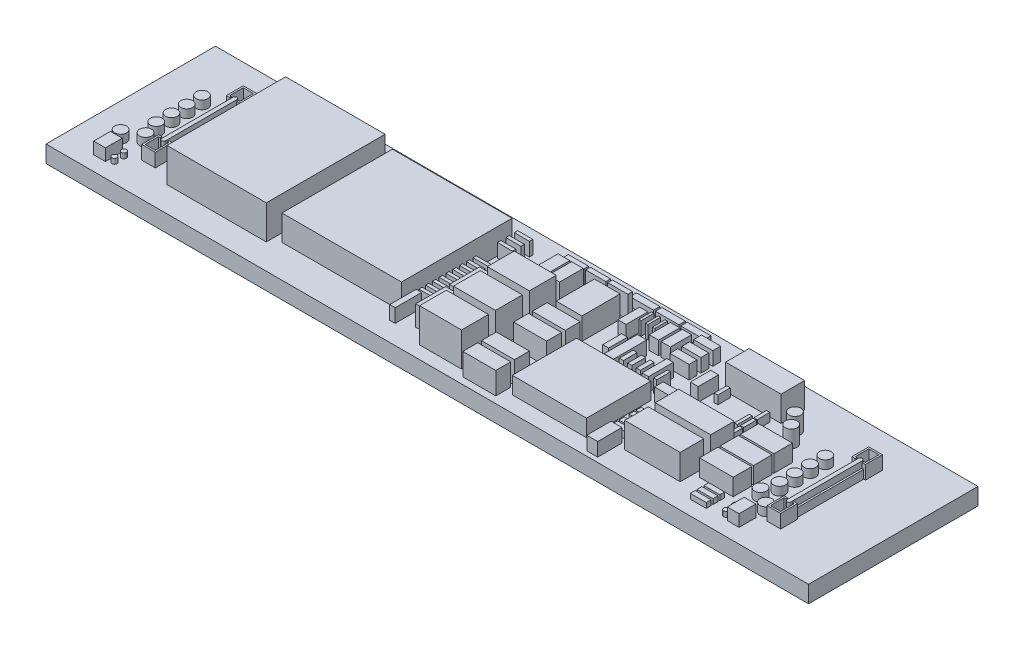
SolidWorks part; units mm, degrees
material "A-Glass Fiber"
ref_plane "Front Plane" through (0, 0, 0) normal (0, 0, 1) x (1, 0, 0)
ref_plane "Top Plane" through (0, 0, 0) normal (0, 1, 0) x (1, 0, 0)
ref_plane "Right Plane" through (0, 0, 0) normal (1, 0, 0) x (0, 0, -1)
sketch "Sketch1" plane through (0, 0, 0) normal (0, 1, 0) x (1, 0, 0)
  line L1 (22.5, 5) -> (-22.5, 5)
  line L2 (22.5, 5) -> (22.5, -5)
  line L3 (22.5, -5) -> (-22.5, -5)
  line L4 (-22.5, 5) -> (-22.5, -5)
  line L5 (22.5, 5) -> (-22.5, -5) construction
  line L6 (22.5, -5) -> (-22.5, 5) construction
  point P0 (0, 0)
  dimension "D1" = 10
  dimension "D2" = 45
extrude "Boss-Extrude1" add sketch "Sketch1" along normal blind 1
sketch "Sketch7" plane through (0, 1, 0) normal (0, 1, 0) x (1, 0, 0)
  line L0 (18.0549, 3) -> (18.8549, 3)
  line L1 (18.8549, 3) -> (18.8549, 2)
  line L2 (18.0549, 3) -> (18.0549, 2)
  line L3 (18.0549, 2) -> (18.2549, 2)
  line L5 (18.8549, 2) -> (18.6549, 2)
  line L6 (18.6549, 2) -> (18.6549, 0)
  line L7 (18.3549, 2.1) -> (18.3549, 0)
  line L8 (22.5, 5) -> (-22.5, 5) construction
  line L9 (22.5, 0) -> (-21.2933, 0) construction
  line L10 (22.5, -5) -> (22.5, 5) construction
  line L11 (18.1549, 2.1) -> (18.2549, 2.1)
  line L12 (18.1549, 2.9) -> (18.1549, 2.1)
  line L13 (18.1549, 2.9) -> (18.7549, 2.9)
  line L14 (18.7549, 2.9) -> (18.7549, 2.1)
  line L15 (18.7549, 2.1) -> (18.6549, 2.1)
  line L16 (18.5549, 2.1) -> (18.5549, 0)
  line L17 (18.2549, 2) -> (18.2549, 2.1)
  line L18 (18.6549, 2) -> (18.6549, 2.1)
  line L19 (18.1549, 2.1) -> (18.3549, 2.1) construction
  line L20 (18.7549, 2.1) -> (18.5549, 2.1) construction
  line L21 (18.2549, 2) -> (18.2549, 0) construction
  dimension "D1" = 1
  dimension "D2" = 0.8
  dimension "D3" = 0.2
  dimension "D4" = 0.2
  dimension "D5" = 2
  dimension "D6" = 0.1
extrude "Boss-Extrude4" add sketch "Sketch7" along normal blind 0.8 contours L18 L5 L1 L0 L2 L3 L17 L11 L12 L13 L14 L15 region at (18.4549, 1, -2.9872)
sketch "Sketch8" plane through (0, 1, 0) normal (0, 1, 0) x (1, 0, 0)
  line L0 (18.1549, 2) -> (18.1549, -2)
  line L1 (18.0549, 2) -> (18.2549, 2) construction
  line L3 (18.2647, -2) -> (18.2647, 2)
  line L4 (18.0549, 2) -> (18.2549, 2) construction
  line L5 (18.2647, 2) -> (18.1549, 2)
  line L6 (18.1549, -2) -> (18.2647, -2)
  line L8 (18.645, 2) -> (18.7549, 2)
  line L9 (18.645, -2) -> (18.645, 2)
  line L10 (18.7549, 2) -> (18.7549, -2)
  line L11 (22.5, 0) -> (-0.6282, 0) construction
  line L12 (22.5, -5) -> (22.5, 5) construction
  line L13 (18.645, -2) -> (18.7549, -2)
  point P9 (18.7549, 0)
  point P11 (18.645, 0)
  point P15 (18.2647, 0)
  point P23 (18.1549, 0)
extrude "Boss-Extrude5" add sketch "Sketch8" along normal blind 0.5
mirror "Mirror1" about plane through (0, 0, 0) normal (0, 0, 1) of "Boss-Extrude4"
sketch "Sketch9" plane through (0, 1, 0) normal (0, 1, 0) x (1, 0, 0)
  line L0 (18.4549, 2.1) -> (18.4549, -2.1) construction
  line L2 (18.4549, 2.1) -> (18.4549, -2.1) construction
  line L3 (18.5737, 2.1) -> (18.5737, -2.1)
  line L4 (18.336, 2.1) -> (18.336, -2.1)
  arc A0 (18.5737, 2.1) -> (18.336, 2.1) centre (18.4549, 2.1) ccw
  arc A1 (18.336, -2.1) -> (18.5737, -2.1) centre (18.4549, -2.1) ccw
  point P2 (18.4549, 0)
extrude "Boss-Extrude6" add sketch "Sketch9" along normal blind 0.8
mirror "Mirror2" about plane through (0, 0, 0) normal (1, 0, 0) of "Boss-Extrude6", "Mirror1", "Boss-Extrude5", "Boss-Extrude4"
sketch "Sketch10" plane through (0, 1, 0) normal (0, 1, 0) x (1, 0, 0)
  line L0 (16.8488, -4.144) -> (17.5436, -4.144)
  line L1 (17.5436, -4.144) -> (17.5436, -3.1514)
  line L2 (17.5436, -3.1514) -> (16.8488, -3.1514)
  line L3 (16.8488, -3.1514) -> (16.8488, -4.144)
extrude "Boss-Extrude7" add sketch "Sketch10" along normal blind 0.7
sketch "Sketch11" plane through (0, 1, 0) normal (0, 1, 0) x (1, 0, 0)
  circle A0 centre (17.5436, -2.5555) radius 0.35
  circle A1 centre (16.5477, -3.908) radius 0.15
  circle A2 centre (16.5477, -3.3563) radius 0.15
  dimension "D1" = 0.7
  dimension "D2" = 0.3
  dimension "D3" = 0.3
extrude "Boss-Extrude8" add sketch "Sketch11" along normal blind 0.5 contours A0 region at (17.5436, 1, 2.5555)
extrude "Boss-Extrude9" add sketch "Sketch11<3>" along normal blind 0.3 contours A1 | A2 region at (16.5477, 1, 3.908) region at (16.5477, 1, 3.3563)
sketch "Sketch11<3>" plane through (0, 1, 0) normal (0, 1, 0) x (1, 0, 0) same geometry as "Sketch11"
sketch "Sketch12" plane through (0, 1, 0) normal (0, 1, 0) x (1, 0, 0)
  circle A0 centre (16.6479, -1.9784) radius 0.35
  circle A1 centre (16.8903, -1.103) radius 0.35
  circle A2 centre (16.8903, -0.203) radius 0.35
  circle A3 centre (16.8903, 0.697) radius 0.35
  circle A4 centre (16.8903, 1.597) radius 0.35
  dimension "D1" = 0.7
  dimension "D2" = 0.7
  dimension "D3" = 4
extrude "Boss-Extrude10" add sketch "Sketch12" along normal blind 0.5
sketch "Sketch13" plane through (0, 1, 0) normal (0, 1, 0) x (1, 0, 0)
  line L0 (16.8488, -4.144) -> (-26.6256, -4.144) construction
  line L1 (14.6652, -4.144) -> (15.6081, -4.144)
  line L2 (15.6081, -4.144) -> (15.6081, -3.8538)
  line L3 (15.6081, -3.8538) -> (14.6652, -3.8538)
  line L4 (14.6652, -3.8538) -> (14.6652, -4.144)
  line L5 (14.6652, -3.4538) -> (14.6652, -3.744)
  line L6 (14.6652, -3.744) -> (15.6081, -3.744)
  line L7 (15.6081, -3.744) -> (15.6081, -3.4538)
  line L8 (15.6081, -3.4538) -> (14.6652, -3.4538)
  line L9 (14.6652, -3.0538) -> (14.6652, -3.344)
  line L10 (14.6652, -3.344) -> (15.6081, -3.344)
  line L11 (15.6081, -3.344) -> (15.6081, -3.0538)
  line L12 (15.6081, -3.0538) -> (14.6652, -3.0538)
  dimension "D1" = 3
extrude "Boss-Extrude11" add sketch "Sketch13" along normal blind 0.3
sketch "Sketch14" plane through (0, 1, 0) normal (0, 1, 0) x (1, 0, 0)
  line L0 (13.8215, -0.4625) -> (15.8066, -1.5544) construction
  line L1 (13.8215, -1.6625) -> (15.8066, -1.6625)
  line L2 (13.8215, -1.6625) -> (13.8215, -2.7544)
  line L3 (13.8215, -2.7544) -> (15.8066, -2.7544)
  line L4 (15.8066, -1.6625) -> (15.8066, -2.7544)
  line L5 (13.8215, -1.6625) -> (15.8066, -2.7544) construction
  line L6 (13.8215, -2.7544) -> (15.8066, -1.6625) construction
  line L7 (13.8215, -1.5544) -> (15.8066, -0.4625) construction
  line L8 (13.8215, -0.4625) -> (13.8215, -1.5544)
  line L9 (13.8215, -0.4625) -> (15.8066, -0.4625)
  line L10 (15.8066, -0.4625) -> (15.8066, -1.5544)
  line L11 (13.8215, -1.5544) -> (15.8066, -1.5544)
  line L12 (13.8215, 0.7375) -> (15.8066, -0.3544) construction
  line L13 (13.8215, -0.3544) -> (15.8066, 0.7375) construction
  line L14 (13.8215, 0.7375) -> (13.8215, -0.3544)
  line L15 (13.8215, 0.7375) -> (15.8066, 0.7375)
  line L16 (15.8066, 0.7375) -> (15.8066, -0.3544)
  line L17 (13.8215, -0.3544) -> (15.8066, -0.3544)
  circle A0 centre (14.814, 1.6625) radius 0.35
  circle A1 centre (14.2743, 2.4227) radius 0.35
  point P0 (14.814, -2.2085)
  point P7 (14.814, -1.0085)
  point P12 (14.814, 0.1915)
  dimension "D2" = 0.7
  dimension "D3" = 0.7
  dimension "D1" = 3
extrude "Boss-Extrude12" add sketch "Sketch14" along normal blind 1
sketch "Sketch15" plane through (0, 1, 0) normal (0, 1, 0) x (1, 0, 0)
  line L0 (10.1986, -1.7484) -> (13.4741, -1.7484)
  line L1 (10.1986, -2.1588) -> (13.4741, -2.1588)
  line L2 (10.1986, -2.1588) -> (10.1986, -3.5484)
  line L3 (10.1986, -3.5484) -> (13.4741, -3.5484)
  line L4 (13.4741, -2.1588) -> (13.4741, -3.5484)
  line L5 (10.1986, -2.1588) -> (13.4741, -3.5484) construction
  line L6 (10.1986, -3.5484) -> (13.4741, -2.1588) construction
  line L7 (10.1986, -0.3588) -> (10.1986, -1.7484)
  line L8 (10.1986, -0.3588) -> (13.4741, -0.3588)
  line L9 (13.4741, -0.3588) -> (13.4741, -1.7484)
  line L12 (12.8746, 0.542) -> (13.0731, 0.542)
  line L13 (12.8746, 0.542) -> (12.8746, -0.1992)
  line L14 (12.8746, -0.1992) -> (13.0731, -0.1992)
  line L15 (13.0731, 0.542) -> (13.0731, -0.1992)
  line L16 (12.8746, 0.542) -> (13.0731, -0.1992) construction
  line L17 (12.8746, -0.1992) -> (13.0731, 0.542) construction
  point P0 (11.8363, -2.8536)
  point P11 (12.9738, 0.1714)
  dimension "D1" = 2
extrude "Boss-Extrude13" add sketch "Sketch15" along normal blind 1.5 contours L9 L8 L7 L0 | L4 L1 L2 L3 region at (11.8363, 1, 1.0536) region at (11.8363, 1, 2.8536)
extrude "Boss-Extrude14" add sketch "Sketch15<3>" along normal blind 0.5 contours L13 L14 L15 L12
sketch "Sketch15<3>" plane through (0, 1, 0) normal (0, 1, 0) x (1, 0, 0) same geometry as "Sketch15"
pattern_linear "LPattern1" count 3 spacing 0.8 along (0, 0, -1) of "Boss-Extrude14"
sketch "Sketch16" plane through (0, 1, 0) normal (0, 1, 0) x (1, 0, 0)
  line L0 (13.4741, 3.7966) -> (13.4741, 2.407)
  line L1 (13.4741, 2.407) -> (10.1986, 2.407)
  line L2 (10.1986, 2.407) -> (10.1986, 3.7966)
  line L3 (10.1986, 3.7966) -> (13.4741, 3.7966)
  line L4 (10.1986, -0.3588) -> (10.1986, -1.7484) construction
extrude "Boss-Extrude15" add sketch "Sketch16" along normal blind 1.5
sketch "Sketch17" plane through (0, 1, 0) normal (0, 1, 0) x (1, 0, 0)
  line L1 (11.6786, -0.2357) -> (12.6496, -0.2357)
  line L2 (11.6786, -0.2357) -> (11.6786, 0.0129)
  line L3 (11.6786, 0.0129) -> (12.6496, 0.0129)
  line L4 (12.6496, -0.2357) -> (12.6496, 0.0129)
  line L5 (11.6786, -0.2357) -> (12.6496, 0.0129) construction
  line L6 (11.6786, 0.0129) -> (12.6496, -0.2357) construction
  line L7 (10.4418, 2.2288) -> (10.6522, 2.2288)
  line L8 (10.4418, 2.2288) -> (10.4418, 1.4925)
  line L9 (10.4418, 1.4925) -> (10.6522, 1.4925)
  line L10 (10.6522, 2.2288) -> (10.6522, 1.4925)
  line L11 (10.4418, 2.2288) -> (10.6522, 1.4925) construction
  line L12 (10.4418, 1.4925) -> (10.6522, 2.2288) construction
  line L13 (12.7367, 1.4426) -> (12.5625, 1.4426)
  line L14 (12.7367, 1.4426) -> (12.7367, 0.5591)
  line L15 (12.7367, 0.5591) -> (12.5625, 0.5591)
  line L16 (12.5625, 1.4426) -> (12.5625, 0.5591)
  line L17 (12.7367, 1.4426) -> (12.5625, 0.5591) construction
  line L18 (12.7367, 0.5591) -> (12.5625, 1.4426) construction
  point P0 (12.1641, -0.1114)
  point P6 (12.6496, 1.0009)
  point P7 (10.547, 1.8607)
extrude "Boss-Extrude16" add sketch "Sketch17" along normal blind 0.5
sketch "Sketch19" plane through (0, 1, 0) normal (0, 1, 0) x (1, 0, 0)
  line L1 (9.1377, -4.7245) -> (9.7804, -4.7245)
  line L2 (9.1377, -4.7245) -> (9.1377, -3.2947)
  line L3 (9.1377, -3.2947) -> (9.7804, -3.2947)
  line L4 (9.7804, -4.7245) -> (9.7804, -3.2947)
  line L5 (9.1377, -4.7245) -> (9.7804, -3.2947) construction
  line L6 (9.1377, -3.2947) -> (9.7804, -4.7245) construction
  point P0 (9.4591, -4.0096)
extrude "Boss-Extrude17" add sketch "Sketch19" along normal blind 0.8
sketch "Sketch20" plane through (0, 1, 0) normal (0, 1, 0) x (1, 0, 0)
  line L0 (9.8976, -2.2877) -> (9.8976, -2.6011)
  line L1 (9.8976, -2.6877) -> (8.9103, -2.6877)
  line L2 (9.8976, -2.6877) -> (9.8976, -3.0011)
  line L3 (9.8976, -3.0011) -> (8.9103, -3.0011)
  line L4 (8.9103, -2.6877) -> (8.9103, -3.0011)
  line L5 (9.8976, -2.6877) -> (8.9103, -3.0011) construction
  line L6 (9.8976, -3.0011) -> (8.9103, -2.6877) construction
  line L7 (9.8976, -2.2877) -> (8.9103, -2.2877)
  line L8 (8.9103, -2.2877) -> (8.9103, -2.6011)
  line L9 (9.8976, -2.6011) -> (8.9103, -2.6011)
  point P0 (9.404, -2.8444)
extrude "Boss-Extrude18" add sketch "Sketch20" along normal blind 0.4
pattern_linear "LPattern2" count 2 spacing 1 along (0, 0, -1) of "Boss-Extrude18"
sketch "Sketch21" plane through (0, 1, 0) normal (0, 1, 0) x (1, 0, 0)
  line L1 (8.6652, 0.2571) -> (9.9933, 0.2571)
  line L2 (8.6652, 0.2571) -> (8.6652, -0.2571)
  line L3 (8.6652, -0.2571) -> (9.9933, -0.2571)
  line L4 (9.9933, 0.2571) -> (9.9933, -0.2571)
  line L5 (8.6652, 0.2571) -> (9.9933, -0.2571) construction
  line L6 (8.6652, -0.2571) -> (9.9933, 0.2571) construction
  line L7 (9.9412, 2.2465) -> (9.4772, 2.2465)
  line L8 (9.9412, 2.2465) -> (9.9412, 1.048)
  line L9 (9.9412, 1.048) -> (9.4772, 1.048)
  line L10 (9.4772, 2.2465) -> (9.4772, 1.048)
  line L11 (9.9412, 2.2465) -> (9.4772, 1.048) construction
  line L12 (9.9412, 1.048) -> (9.4772, 2.2465) construction
  point P0 (9.3293, 0)
  point P5 (9.7092, 1.6473)
extrude "Boss-Extrude19" add sketch "Sketch21" along normal blind 0.8
sketch "Sketch22" plane through (0, 1, 0) normal (0, 1, 0) x (1, 0, 0)
  line L1 (4.0768, -0.2672) -> (8.4598, -0.2672)
  line L2 (4.0768, -0.2672) -> (4.0768, -4.0612)
  line L3 (4.0768, -4.0612) -> (8.4598, -4.0612)
  line L4 (8.4598, -0.2672) -> (8.4598, -4.0612)
  line L5 (4.0768, -0.2672) -> (8.4598, -4.0612) construction
  line L6 (4.0768, -4.0612) -> (8.4598, -0.2672) construction
  point P0 (6.2683, -2.1642)
extrude "Boss-Extrude20" add sketch "Sketch22" along normal blind 1 separate body
sketch "Sketch23" plane through (0, 1, 0) normal (0, 1, 0) x (1, 0, 0)
  line L0 (6.659, 0.982) -> (6.659, 0.1696)
  line L1 (8.1833, 0.982) -> (8.3685, 0.982)
  line L2 (8.1833, 0.982) -> (8.1833, 0.1696)
  line L3 (8.1833, 0.1696) -> (8.3685, 0.1696)
  line L4 (8.3685, 0.982) -> (8.3685, 0.1696)
  line L5 (8.1833, 0.982) -> (8.3685, 0.1696) construction
  line L6 (8.1833, 0.1696) -> (8.3685, 0.982) construction
  line L7 (7.5848, 1.5538) -> (7.9697, 1.5538)
  line L8 (7.5848, 1.5538) -> (7.5848, 0.0866)
  line L9 (7.5848, 0.0866) -> (7.9697, 0.0866)
  line L10 (7.9697, 1.5538) -> (7.9697, 0.0866)
  line L11 (7.5848, 1.5538) -> (7.9697, 0.0866) construction
  line L12 (7.5848, 0.0866) -> (7.9697, 1.5538) construction
  line L13 (7.159, 0.982) -> (7.4031, 0.982)
  line L14 (7.159, 0.982) -> (7.159, 0.1696)
  line L15 (7.159, 0.1696) -> (7.4031, 0.1696)
  line L16 (7.4031, 0.982) -> (7.4031, 0.1696)
  line L17 (7.159, 0.982) -> (7.4031, 0.1696) construction
  line L18 (7.159, 0.1696) -> (7.4031, 0.982) construction
  line L19 (6.659, 0.982) -> (6.9031, 0.982)
  line L20 (6.9031, 0.982) -> (6.9031, 0.1696)
  line L21 (6.659, 0.1696) -> (6.9031, 0.1696)
  line L22 (6.159, 0.982) -> (6.159, 0.1696)
  line L23 (6.159, 0.982) -> (6.4031, 0.982)
  line L24 (6.4031, 0.982) -> (6.4031, 0.1696)
  line L25 (6.159, 0.1696) -> (6.4031, 0.1696)
  line L26 (8.5364, 3.0807) -> (7.4031, 2.6108) construction
  line L27 (5.4875, 1.9108) -> (6.0393, 1.9108)
  line L28 (5.4875, 1.9108) -> (5.4875, -0.0452)
  line L29 (5.4875, -0.0452) -> (6.0393, -0.0452)
  line L30 (6.0393, 1.9108) -> (6.0393, -0.0452)
  line L31 (5.4875, 1.9108) -> (6.0393, -0.0452) construction
  line L32 (5.4875, -0.0452) -> (6.0393, 1.9108) construction
  line L33 (5.3301, 1.4921) -> (4.9811, 1.4921)
  line L34 (5.3301, 1.4921) -> (5.3301, 0.3734)
  line L35 (5.3301, 0.3734) -> (4.9811, 0.3734)
  line L36 (4.9811, 1.4921) -> (4.9811, 0.3734)
  line L37 (5.3301, 1.4921) -> (4.9811, 0.3734) construction
  line L38 (5.3301, 0.3734) -> (4.9811, 1.4921) construction
  line L39 (8.5364, 2.3807) -> (7.4031, 2.3807)
  line L40 (8.5364, 2.3807) -> (8.5364, 1.9108)
  line L41 (8.5364, 1.9108) -> (7.4031, 1.9108)
  line L42 (7.4031, 2.3807) -> (7.4031, 1.9108)
  line L43 (8.5364, 2.3807) -> (7.4031, 1.9108) construction
  line L44 (8.5364, 1.9108) -> (7.4031, 2.3807) construction
  line L45 (8.5364, 2.6108) -> (7.4031, 3.0807) construction
  line L46 (8.5364, 3.0807) -> (8.5364, 2.6108)
  line L47 (8.5364, 3.0807) -> (7.4031, 3.0807)
  line L48 (7.4031, 3.0807) -> (7.4031, 2.6108)
  line L49 (8.5364, 2.6108) -> (7.4031, 2.6108)
  line L50 (8.5364, 3.7807) -> (7.4031, 3.3108) construction
  line L51 (8.5364, 3.3108) -> (7.4031, 3.7807) construction
  line L52 (8.5364, 3.7807) -> (8.5364, 3.3108)
  line L53 (8.5364, 3.7807) -> (7.4031, 3.7807)
  line L54 (7.4031, 3.7807) -> (7.4031, 3.3108)
  line L55 (8.5364, 3.3108) -> (7.4031, 3.3108)
  point P0 (8.2759, 0.5758)
  point P5 (7.7772, 0.8202)
  point P10 (5.7634, 0.9328)
  point P12 (7.281, 0.5758)
  point P28 (5.1556, 0.9328)
  point P33 (7.9697, 2.1457)
  point P40 (7.9697, 2.8457)
  point P45 (7.9697, 3.5457)
extrude "Boss-Extrude21" add sketch "Sketch23" along normal blind 0.8
sketch "Sketch24" plane through (0, 1, 0) normal (0, 1, 0) x (1, 0, 0)
  line L0 (5.8422, 3.5058) -> (6.3976, 2.2514) construction
  line L1 (6.5422, 3.5058) -> (7.0976, 3.5058)
  line L2 (6.5422, 3.5058) -> (6.5422, 2.2514)
  line L3 (6.5422, 2.2514) -> (7.0976, 2.2514)
  line L4 (7.0976, 3.5058) -> (7.0976, 2.2514)
  line L5 (6.5422, 3.5058) -> (7.0976, 2.2514) construction
  line L6 (6.5422, 2.2514) -> (7.0976, 3.5058) construction
  line L7 (5.8422, 2.2514) -> (6.3976, 3.5058) construction
  line L8 (5.8422, 3.5058) -> (5.8422, 2.2514)
  line L9 (5.8422, 3.5058) -> (6.3976, 3.5058)
  line L10 (6.3976, 3.5058) -> (6.3976, 2.2514)
  line L11 (5.8422, 2.2514) -> (6.3976, 2.2514)
  line L12 (5.1476, 2.7378) -> (5.1476, 3.4867)
  line L13 (5.5476, 2.7378) -> (5.6869, 2.7378)
  line L14 (5.5476, 2.7378) -> (5.5476, 3.4867)
  line L15 (5.5476, 3.4867) -> (5.6869, 3.4867)
  line L16 (5.6869, 2.7378) -> (5.6869, 3.4867)
  line L17 (5.5476, 2.7378) -> (5.6869, 3.4867) construction
  line L18 (5.5476, 3.4867) -> (5.6869, 2.7378) construction
  line L19 (5.1476, 2.7378) -> (5.2869, 2.7378)
  line L20 (5.2869, 2.7378) -> (5.2869, 3.4867)
  line L21 (5.1476, 3.4867) -> (5.2869, 3.4867)
  line L22 (4.7476, 2.7378) -> (4.7476, 3.4867)
  line L23 (4.7476, 2.7378) -> (4.8869, 2.7378)
  line L24 (4.8869, 2.7378) -> (4.8869, 3.4867)
  line L25 (4.7476, 3.4867) -> (4.8869, 3.4867)
  line L27 (4.1514, 3.3801) -> (4.6383, 3.3801)
  line L28 (4.1514, 3.3801) -> (4.1514, 2.0955)
  line L29 (4.1514, 2.0955) -> (4.6383, 2.0955)
  line L30 (4.6383, 3.3801) -> (4.6383, 2.0955)
  line L31 (4.1514, 3.3801) -> (4.6383, 2.0955) construction
  line L32 (4.1514, 2.0955) -> (4.6383, 3.3801) construction
  point P0 (6.8199, 2.8786)
  point P5 (5.6172, 3.1123)
  point P7 (6.1199, 2.8786)
  point P15 (4.3948, 2.7378)
  point P17 (5.2172, 3.1123)
  point P22 (4.8172, 3.1123)
extrude "Boss-Extrude22" add sketch "Sketch24" along normal blind 0.8
sketch "Sketch25" plane through (0, 1, 0) normal (0, 1, 0) x (1, 0, 0)
  line L0 (4.5243, 4.3177) -> (5.9167, 3.9347) construction
  line L1 (6.0243, 4.3177) -> (7.4167, 4.3177)
  line L2 (6.0243, 4.3177) -> (6.0243, 3.9347)
  line L3 (6.0243, 3.9347) -> (7.4167, 3.9347)
  line L4 (7.4167, 4.3177) -> (7.4167, 3.9347)
  line L5 (6.0243, 4.3177) -> (7.4167, 3.9347) construction
  line L6 (6.0243, 3.9347) -> (7.4167, 4.3177) construction
  line L7 (4.5243, 3.9347) -> (5.9167, 4.3177) construction
  line L8 (4.5243, 4.3177) -> (4.5243, 3.9347)
  line L9 (4.5243, 4.3177) -> (5.9167, 4.3177)
  line L10 (5.9167, 4.3177) -> (5.9167, 3.9347)
  line L11 (4.5243, 3.9347) -> (5.9167, 3.9347)
  line L12 (3.0243, 4.3177) -> (4.4167, 3.9347) construction
  line L13 (3.0243, 3.9347) -> (4.4167, 4.3177) construction
  line L14 (3.0243, 4.3177) -> (3.0243, 3.9347)
  line L15 (3.0243, 4.3177) -> (4.4167, 4.3177)
  line L16 (4.4167, 4.3177) -> (4.4167, 3.9347)
  line L17 (3.0243, 3.9347) -> (4.4167, 3.9347)
  point P0 (6.7205, 4.1262)
  point P7 (5.2205, 4.1262)
  point P12 (3.7205, 4.1262)
extrude "Boss-Extrude23" add sketch "Sketch25" along normal blind 0.5
sketch "Sketch26" plane through (0, 1, 0) normal (0, 1, 0) x (1, 0, 0)
  line L0 (1.6966, -3.501) -> (3.6446, -2.619) construction
  line L1 (1.6966, -4.601) -> (3.6446, -4.601)
  line L2 (1.6966, -4.601) -> (1.6966, -3.719)
  line L3 (1.6966, -3.719) -> (3.6446, -3.719)
  line L4 (3.6446, -4.601) -> (3.6446, -3.719)
  line L5 (1.6966, -4.601) -> (3.6446, -3.719) construction
  line L6 (1.6966, -3.719) -> (3.6446, -4.601) construction
  line L7 (1.6966, -2.619) -> (3.6446, -3.501) construction
  line L8 (1.6966, -3.501) -> (1.6966, -2.619)
  line L9 (1.6966, -3.501) -> (3.6446, -3.501)
  line L10 (3.6446, -3.501) -> (3.6446, -2.619)
  line L11 (1.6966, -2.619) -> (3.6446, -2.619)
  point P0 (2.6706, -4.16)
  point P7 (2.6706, -3.06)
extrude "Boss-Extrude24" add sketch "Sketch26" along normal blind 1.3
pattern_linear "LPattern3" count 2 spacing 3 along (0, 0, -1) of "Boss-Extrude24"
sketch "Sketch27" plane through (0, 1, 0) normal (0, 1, 0) x (1, 0, 0)
  line L0 (1.1612, 3.4662) -> (1.1612, 3.1873)
  line L1 (1.8812, 2.982) -> (3.3994, 2.982)
  line L2 (1.8812, 2.982) -> (1.8812, 0.7255)
  line L3 (1.8812, 0.7255) -> (3.3994, 0.7255)
  line L4 (3.3994, 2.982) -> (3.3994, 0.7255)
  line L5 (1.8812, 2.982) -> (3.3994, 0.7255) construction
  line L6 (1.8812, 0.7255) -> (3.3994, 2.982) construction
  line L7 (2.4612, 3.4662) -> (3.6517, 3.4662)
  line L8 (2.4612, 3.4662) -> (2.4612, 3.1873)
  line L9 (2.4612, 3.1873) -> (3.6517, 3.1873)
  line L10 (3.6517, 3.4662) -> (3.6517, 3.1873)
  line L11 (2.4612, 3.4662) -> (3.6517, 3.1873) construction
  line L12 (2.4612, 3.1873) -> (3.6517, 3.4662) construction
  line L13 (1.1612, 3.4662) -> (2.3517, 3.4662)
  line L14 (2.3517, 3.4662) -> (2.3517, 3.1873)
  line L15 (1.1612, 3.1873) -> (2.3517, 3.1873)
  line L16 (-0.1388, 3.4662) -> (-0.1388, 3.1873)
  line L17 (-0.1388, 3.4662) -> (1.0517, 3.4662)
  line L18 (1.0517, 3.4662) -> (1.0517, 3.1873)
  line L19 (-0.1388, 3.1873) -> (1.0517, 3.1873)
  point P0 (2.6403, 1.8538)
  point P6 (3.0565, 3.3267)
extrude "Boss-Extrude25" add sketch "Sketch27" along normal blind 1.3
sketch "Sketch28" plane through (0, 1, 0) normal (0, 1, 0) x (1, 0, 0)
  line L0 (-1.2159, -0.6551) -> (-1.2159, -2.2432)
  line L1 (-1.2159, -2.6551) -> (1.2655, -2.6551)
  line L2 (-1.2159, -2.6551) -> (-1.2159, -4.2432)
  line L3 (-1.2159, -4.2432) -> (1.2655, -4.2432)
  line L4 (1.2655, -2.6551) -> (1.2655, -4.2432)
  line L5 (-1.2159, -2.6551) -> (1.2655, -4.2432) construction
  line L6 (-1.2159, -4.2432) -> (1.2655, -2.6551) construction
  line L7 (-1.2159, -0.6551) -> (1.2655, -0.6551)
  line L8 (1.2655, -0.6551) -> (1.2655, -2.2432)
  line L9 (-1.2159, -2.2432) -> (1.2655, -2.2432)
  line L10 (-1.2159, 1.3449) -> (-1.2159, -0.2432)
  line L11 (-1.2159, 1.3449) -> (1.2655, 1.3449)
  line L12 (1.2655, 1.3449) -> (1.2655, -0.2432)
  line L13 (-1.2159, -0.2432) -> (1.2655, -0.2432)
  point P0 (0.0248, -3.4492)
extrude "Boss-Extrude26" add sketch "Sketch28" along normal blind 2
sketch "Sketch29" plane through (0, 1, 0) normal (0, 1, 0) x (1, 0, 0)
  line L0 (-0.282, 2.9959) -> (-0.282, 1.6006)
  line L1 (0.518, 2.9959) -> (1.2128, 2.9959)
  line L2 (0.518, 2.9959) -> (0.518, 1.6006)
  line L3 (0.518, 1.6006) -> (1.2128, 1.6006)
  line L4 (1.2128, 2.9959) -> (1.2128, 1.6006)
  line L5 (0.518, 2.9959) -> (1.2128, 1.6006) construction
  line L6 (0.518, 1.6006) -> (1.2128, 2.9959) construction
  line L7 (-0.282, 2.9959) -> (0.4128, 2.9959)
  line L8 (0.4128, 2.9959) -> (0.4128, 1.6006)
  line L9 (-0.282, 1.6006) -> (0.4128, 1.6006)
  point P0 (0.8654, 2.2982)
extrude "Boss-Extrude27" add sketch "Sketch29" along normal blind 1.5
sketch "Sketch30" plane through (0, 1, 0) normal (0, 1, 0) x (1, 0, 0)
  line L0 (-0.6038, 3.4259) -> (-0.6038, 2.4915)
  line L1 (-0.6038, 2.4259) -> (-0.4389, 2.4259)
  line L2 (-0.6038, 2.4259) -> (-0.6038, 1.4915)
  line L3 (-0.6038, 1.4915) -> (-0.4389, 1.4915)
  line L4 (-0.4389, 2.4259) -> (-0.4389, 1.4915)
  line L5 (-0.6038, 2.4259) -> (-0.4389, 1.4915) construction
  line L6 (-0.6038, 1.4915) -> (-0.4389, 2.4259) construction
  line L7 (-0.6038, 3.4259) -> (-0.4389, 3.4259)
  line L8 (-0.4389, 3.4259) -> (-0.4389, 2.4915)
  line L9 (-0.6038, 2.4915) -> (-0.4389, 2.4915)
  point P0 (-0.5213, 1.9587)
  point P7 (-0.5213, 2.9587)
extrude "Boss-Extrude28" add sketch "Sketch30" along normal blind 0.8
sketch "Sketch31" plane through (0, 1, 0) normal (0, 1, 0) x (1, 0, 0)
  line L0 (-2.2238, 0.3041) -> (-2.2238, -1.4575)
  line L1 (-2.2238, -1.6959) -> (-1.5191, -1.6959)
  line L2 (-2.2238, -1.6959) -> (-2.2238, -3.4575)
  line L3 (-2.2238, -3.4575) -> (-1.5191, -3.4575)
  line L4 (-1.5191, -1.6959) -> (-1.5191, -3.4575)
  line L5 (-2.2238, -1.6959) -> (-1.5191, -3.4575) construction
  line L6 (-2.2238, -3.4575) -> (-1.5191, -1.6959) construction
  line L7 (-2.2238, 0.3041) -> (-1.5191, 0.3041)
  line L8 (-1.5191, 0.3041) -> (-1.5191, -1.4575)
  line L9 (-2.2238, -1.4575) -> (-1.5191, -1.4575)
  point P0 (-1.8714, -2.5767)
extrude "Boss-Extrude29" add sketch "Sketch31" along normal blind 1.2
sketch "Sketch32" plane through (0, 1, 0) normal (0, 1, 0) x (1, 0, 0)
  line L1 (-10.5138, 3.4572) -> (-3.456, 3.4572)
  line L2 (-10.5138, 3.4572) -> (-10.5138, -3.0643)
  line L3 (-10.5138, -3.0643) -> (-3.456, -3.0643)
  line L4 (-3.456, 3.4572) -> (-3.456, -3.0643)
  line L5 (-10.5138, 3.4572) -> (-3.456, -3.0643) construction
  line L6 (-10.5138, -3.0643) -> (-3.456, 3.4572) construction
  point P0 (-6.9849, 0.1964)
extrude "Boss-Extrude30" add sketch "Sketch32" along normal blind 1.5 separate body
sketch "Sketch33" plane through (0, 1, 0) normal (0, 1, 0) x (1, 0, 0)
  line L1 (-3.3545, -2.3046) -> (-3.0293, -2.3046)
  line L2 (-3.3545, -2.3046) -> (-3.3545, -3.8654)
  line L3 (-3.3545, -3.8654) -> (-3.0293, -3.8654)
  line L4 (-3.0293, -2.3046) -> (-3.0293, -3.8654)
  line L5 (-3.3545, -2.3046) -> (-3.0293, -3.8654) construction
  line L6 (-3.3545, -3.8654) -> (-3.0293, -2.3046) construction
  point P0 (-3.1919, -3.085)
extrude "Boss-Extrude31" add sketch "Sketch33" along normal blind 0.8
sketch "Sketch34" plane through (0, 1, 0) normal (0, 1, 0) x (1, 0, 0)
  line L0 (-3.3888, -1.7095) -> (-3.3888, -1.5191)
  line L1 (-3.3888, -2.1095) -> (-2.4766, -2.1095)
  line L2 (-3.3888, -2.1095) -> (-3.3888, -1.9191)
  line L3 (-3.3888, -1.9191) -> (-2.4766, -1.9191)
  line L4 (-2.4766, -2.1095) -> (-2.4766, -1.9191)
  line L5 (-3.3888, -2.1095) -> (-2.4766, -1.9191) construction
  line L6 (-3.3888, -1.9191) -> (-2.4766, -2.1095) construction
  line L7 (-3.3888, -1.7095) -> (-2.4766, -1.7095)
  line L8 (-2.4766, -1.7095) -> (-2.4766, -1.5191)
  line L9 (-3.3888, -1.5191) -> (-2.4766, -1.5191)
  line L10 (-3.3888, -1.3095) -> (-3.3888, -1.1191)
  line L11 (-3.3888, -1.3095) -> (-2.4766, -1.3095)
  line L12 (-2.4766, -1.3095) -> (-2.4766, -1.1191)
  line L13 (-3.3888, -1.1191) -> (-2.4766, -1.1191)
  line L14 (-3.3888, -0.9095) -> (-3.3888, -0.7191)
  line L15 (-3.3888, -0.9095) -> (-2.4766, -0.9095)
  line L16 (-2.4766, -0.9095) -> (-2.4766, -0.7191)
  line L17 (-3.3888, -0.7191) -> (-2.4766, -0.7191)
  line L18 (-3.3888, -0.5095) -> (-3.3888, -0.3191)
  line L19 (-3.3888, -0.5095) -> (-2.4766, -0.5095)
  line L20 (-2.4766, -0.5095) -> (-2.4766, -0.3191)
  line L21 (-3.3888, -0.3191) -> (-2.4766, -0.3191)
  line L22 (-3.3888, -0.1095) -> (-3.3888, 0.0809)
  line L23 (-3.3888, -0.1095) -> (-2.4766, -0.1095)
  line L24 (-2.4766, -0.1095) -> (-2.4766, 0.0809)
  line L25 (-3.3888, 0.0809) -> (-2.4766, 0.0809)
  line L26 (-3.3888, 0.2905) -> (-3.3888, 0.4809)
  line L27 (-3.3888, 0.2905) -> (-2.4766, 0.2905)
  line L28 (-2.4766, 0.2905) -> (-2.4766, 0.4809)
  line L29 (-3.3888, 0.4809) -> (-2.4766, 0.4809)
  line L30 (-3.3888, 0.6905) -> (-3.3888, 0.8809)
  line L31 (-3.3888, 0.6905) -> (-2.4766, 0.6905)
  line L32 (-2.4766, 0.6905) -> (-2.4766, 0.8809)
  line L33 (-3.3888, 0.8809) -> (-2.4766, 0.8809)
  line L34 (-3.3888, 1.0905) -> (-3.3888, 1.2809)
  line L35 (-3.3888, 1.0905) -> (-2.4766, 1.0905)
  line L36 (-2.4766, 1.0905) -> (-2.4766, 1.2809)
  line L37 (-3.3888, 1.2809) -> (-2.4766, 1.2809)
  point P0 (-2.9327, -2.0143)
extrude "Boss-Extrude32" add sketch "Sketch34" along normal blind 0.7
sketch "Sketch35" plane through (0, 1, 0) normal (0, 1, 0) x (1, 0, 0)
  line L0 (-3.3511, 3.1893) -> (-3.3511, 2.9889)
  line L1 (-3.3511, 2.6893) -> (-2.4605, 2.6893)
  line L2 (-3.3511, 2.6893) -> (-3.3511, 2.4889)
  line L3 (-3.3511, 2.4889) -> (-2.4605, 2.4889)
  line L4 (-2.4605, 2.6893) -> (-2.4605, 2.4889)
  line L5 (-3.3511, 2.6893) -> (-2.4605, 2.4889) construction
  line L6 (-3.3511, 2.4889) -> (-2.4605, 2.6893) construction
  line L7 (-3.3511, 3.1893) -> (-2.4605, 3.1893)
  line L8 (-2.4605, 3.1893) -> (-2.4605, 2.9889)
  line L9 (-3.3511, 2.9889) -> (-2.4605, 2.9889)
  line L10 (-3.3511, 3.6893) -> (-3.3511, 3.4889)
  line L11 (-3.3511, 3.6893) -> (-2.4605, 3.6893)
  line L12 (-2.4605, 3.6893) -> (-2.4605, 3.4889)
  line L13 (-3.3511, 3.4889) -> (-2.4605, 3.4889)
  point P0 (-2.9058, 2.5891)
  point P6 (-2.9058, 3.0891)
  point P12 (-2.9058, 3.5891)
extrude "Boss-Extrude33" add sketch "Sketch35" along normal blind 0.8
sketch "Sketch36" plane through (0, 1, 0) normal (0, 1, 0) x (1, 0, 0)
  line L1 (-16.8634, 3.505) -> (-10.993, 3.505)
  line L2 (-16.8634, 3.505) -> (-16.8634, -3.505)
  line L3 (-16.8634, -3.505) -> (-10.993, -3.505)
  line L4 (-10.993, 3.505) -> (-10.993, -3.505)
  line L5 (-16.8634, 3.505) -> (-10.993, -3.505) construction
  line L6 (-16.8634, -3.505) -> (-10.993, 3.505) construction
  point P0 (-13.9282, 0)
extrude "Boss-Extrude34" add sketch "Sketch36" along normal blind 2 separate body
ref_plane "Plane1" through (-1.5, 0, 0) normal (1, 0, 0) x (0, 0, -1)
mirror "Mirror3" about plane through (-1.5, 0, 0) normal (1, 0, 0) of "Boss-Extrude10", "Boss-Extrude9", "Boss-Extrude8", "Boss-Extrude7"
